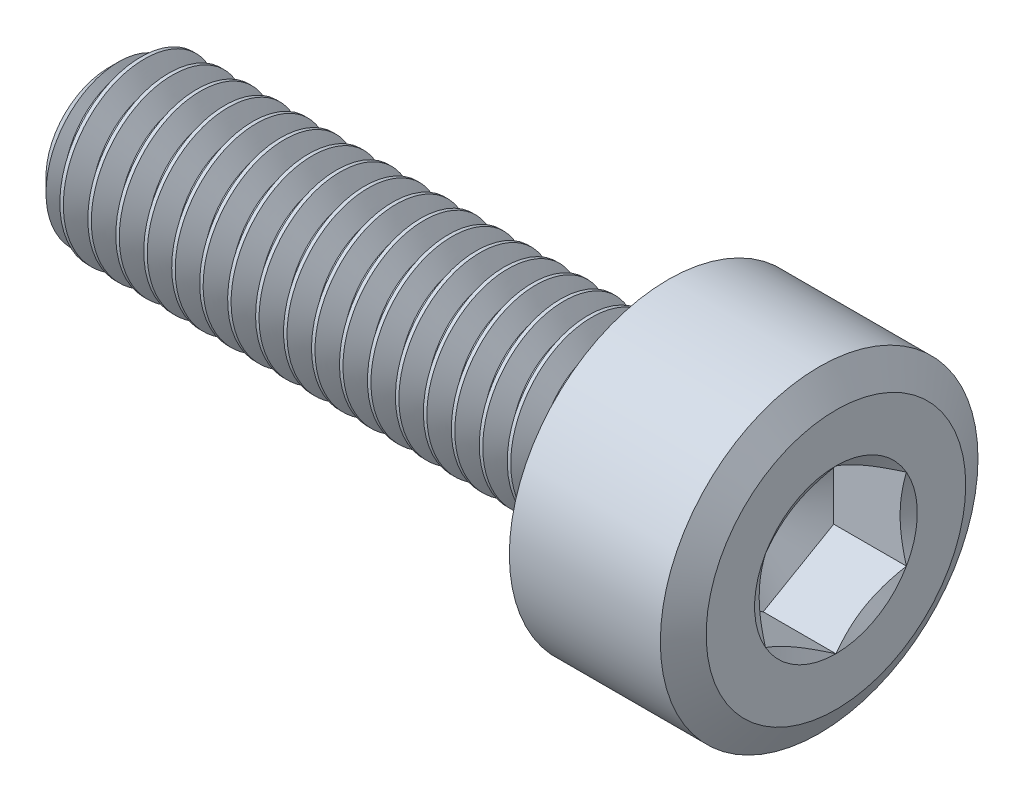
SolidWorks part; units mm, degrees
ref_plane "Front Plane" through (0, 0, 0) normal (0, 0, 1) x (1, 0, 0)
ref_plane "Top Plane" through (0, 0, 0) normal (0, 1, 0) x (1, 0, 0)
ref_plane "Right Plane" through (0, 0, 0) normal (1, 0, 0) x (0, 0, -1)
sketch "Sketch1" plane through (0, 0, 0) normal (0, 0, 1) x (1, 0, 0)
  line L0 (6.5, 2.84) -> (6.5, -2.84) construction
  line L1 (6.5, 0) -> (-6.5, 0) construction
  line L2 (-6.5, 1.5) -> (-6.5, -1.5) construction
  line L3 (-6.5, 1.5) -> (3.5, 1.5) construction
  line L4 (6.5, 2.84) -> (3.5, 2.84) construction
  line L5 (6.5, 1.26) -> (5.2, 1.26) construction
  point P4 (6.5, 1.26)
  point P10 (-5.25, -1.5)
  point P12 (-6, 1.5)
  point P14 (3.5, 1.8)
  point P15 (4.65, 0)
  point P16 (6.2, 2.84)
  dimension "Length" = 10
  dimension "D | Screw Size Decimal Equivalent" = 3
  dimension "Thread Pitch" = 0.5
  dimension "S | Drive Size" = 2.52
  dimension "H | Head Diameter" = 5.68
  dimension "K | Head Height" = 3
  dimension "D1" = 1.25
  dimension "C" = 0.3
  dimension "F" = 3.6
  dimension "T" = 1.3
  dimension "W" = 1.15
sketch "Sketch2" plane through (0, 0, 0) normal (0, 0, 1) x (1, 0, 0)
  line L0 (-6.5, 1.125) -> (-6.5, 0)
  line L1 (-6.5, 0) -> (5.2, 0)
  line L3 (-6.125, 1.5) -> (3.2, 1.5)
  line L7 (-6.5, 1.125) -> (-6.125, 1.5)
  line L10 (-6.5, 1.5) -> (3.5, 1.5) construction
  line L11 (3.5, 2.84) -> (3.5, 1.8)
  line L12 (3.5, 2.84) -> (6.2, 2.84)
  line L13 (6.2, 2.84) -> (6.5, 2.3204)
  line L14 (6.5, 2.84) -> (6.5, -2.84) construction
  line L15 (6.5, 2.3204) -> (6.5, 1.26)
  line L16 (6.5, 1.26) -> (5.2, 1.26)
  line L19 (6.5, 0) -> (-6.5, 0) construction
  line L20 (5.2, 1.26) -> (5.2, 0)
  line L21 (6.5, 2.84) -> (3.5, 2.84) construction
  arc A0 (3.5, 1.8) -> (3.2, 1.5) centre (3.2, 1.8) cw
  dimension "D1" = 45
  dimension "D2" = 0.375
  dimension "D4" = 30
revolve "Revolve1" add sketch "Sketch2" angle 360 about L1
sketch "Sketch3" plane through (6.5, 0, 0) normal (1, 0, 0) x (0, 0, -1)
  line L0 (0, 1.5) -> (0, -1.5) construction
  line L1 (0, 1.4549) -> (-1.26, 0.7275)
  line L2 (-1.26, 0.7275) -> (-1.26, -0.7275)
  line L3 (-1.26, -0.7275) -> (0, -1.4549)
  line L4 (0, -1.4549) -> (1.26, -0.7275)
  line L5 (1.26, -0.7275) -> (1.26, 0.7275)
  line L6 (1.26, 0.7275) -> (0, 1.4549)
  circle A0 centre (0, 0) radius 1.26 construction
extrude "Cut-Extrude1" cut sketch "Sketch3" against normal up to vertex (1.3 mm away) up to point (5.2, 1.26, 0)
sketch "Sketch4" plane through (6.5, 0, 0) normal (1, 0, 0) x (0, 0, -1)
  line L0 (0, 1.5) -> (0, -1.5) construction
  circle A0 centre (0, 0) radius 1.4549
extrude "Cut-Extrude2" cut sketch "Sketch4" against normal through all draft 60
sketch "Sketch7" plane through (5.2, 0, 0) normal (1, 0, 0) x (0, 0, -1)
  line L0 (0, 1.5) -> (0, -1.5) construction
  circle A0 centre (0, 0) radius 1.4549
extrude "Cut-Extrude3" cut sketch "Sketch7" against normal up to vertex (0.55 mm away) draft 60 up to point (4.65, 0, 0)
ref_axis "Center Axis 1" through (6.5, 0, 0) along (-1, 0, 0)
ref_plane "Plane1" through (3.2, 0, 0) normal (1, 0, 0) x (0, 0, -1)
split "Split1" trim tools "Plane1" bodies to split 111 resulting bodies 107 108
sketch "Sketch5" plane through (0, 0, 0) normal (0, 0, 1) x (1, 0, 0)
  line L0 (-6.9375, 1.5) -> (-6.5, 1.5) construction
  line L1 (-6.5, 1.5) -> (-6.7188, 1.1211) construction
  line L2 (-6.7188, 1.1211) -> (-6.9375, 1.5) construction
  line L3 (-6.9375, 1.5) -> (-6.9688, 1.5541) construction
  line L4 (-6.9688, 1.5541) -> (-6.4688, 1.5541) construction
  line L5 (-6.4688, 1.5541) -> (-6.5, 1.5) construction
  line L6 (-6.75, 1.1752) -> (-6.6875, 1.1752) construction
  line L7 (-6.7188, 1.1752) -> (-6.7188, 1.1211) construction
  line L8 (-6.7188, 1.5541) -> (-6.7188, 1.5) construction
  line L9 (-6.9531, 1.5271) -> (-6.4844, 1.5271)
  line L10 (-6.4844, 1.5271) -> (-6.6875, 1.1752)
  line L11 (-6.6875, 1.1752) -> (-6.75, 1.1752)
  line L12 (-6.75, 1.1752) -> (-6.9531, 1.5271)
  dimension "D1" = 0.5
  dimension "D2" = 0.0625
sketch "Sketch6" plane through (-6.5, 0, 0) normal (-1, 0, 0) x (0, 0, 1)
  line L0 (0, 1.5) -> (0, -1.5) construction
  circle A0 centre (0, 0) radius 1.5
curve "Helix/Spiral1" pitch 0.5 height 10.5 radius 1.5 centre (-6.5, 0, 0) axis (1, 0, 0) start towards (0, 1, 0)
sweep "Cut-Sweep1" cut profiles "Sketch5" path "Helix/Spiral1" align with end faces yes
combine bodies "Combine1" operation type add bodies to combine 109 107
equation "\"D1@Sketch1\"=\"Thread Pitch@Sketch1\"*2.5"
equation "\"D1\"= \"K | Head Height@Sketch1\" * .75"
equation "\"D1@Sketch5\"=\"Thread Pitch@Sketch1\""
equation "\"D2@Sketch5\"=\"Thread Pitch@Sketch1\"/8"
equation "\"D3@Helix/Spiral1\" = \"Length@Sketch1\" + \"Thread Pitch@Sketch1\""
equation "\"D4@Helix/Spiral1\"=\"Thread Pitch@Sketch1\""
equation "\"D2@Sketch2\"=\"Thread Pitch@Sketch1\"*.75"
